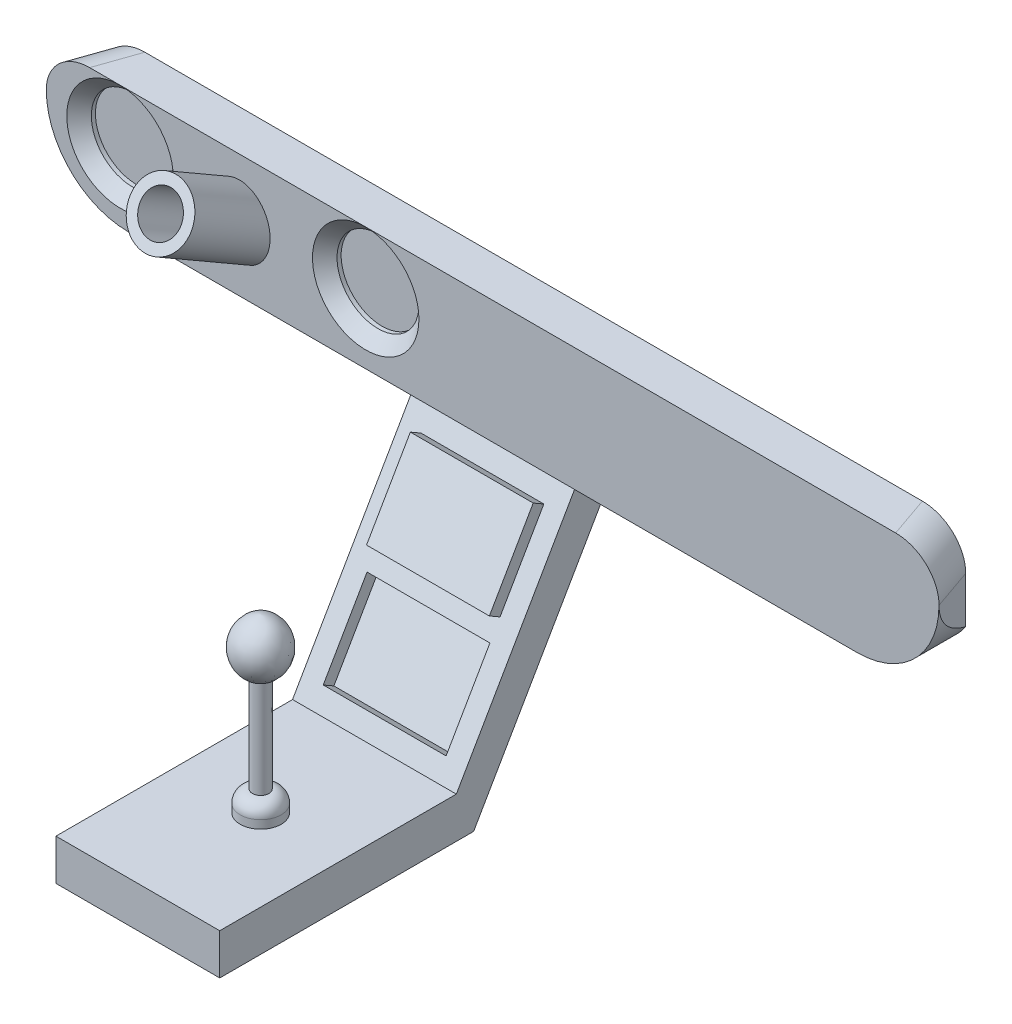
SolidWorks part; units mm, degrees
ref_plane "Ön Düzlem" through (0, 0, 0) normal (0, 0, 1) x (1, 0, 0)
ref_plane "Üst Düzlem" through (0, 0, 0) normal (0, 1, 0) x (1, 0, 0)
ref_plane "Sağ Düzlem" through (0, 0, 0) normal (1, 0, 0) x (0, 0, -1)
sketch "Çizim1" plane through (0, 0, 0) normal (0, 0, 1) x (1, 0, 0)
  line L1 (109, -15) -> (-109, -15)
  line L2 (109, -15) -> (109, 15)
  line L3 (109, 15) -> (-109, 15)
  line L4 (-109, -15) -> (-109, 15)
  line L5 (109, -15) -> (-109, 15) construction
  line L6 (109, 15) -> (-109, -15) construction
  point P0 (0, 0)
  dimension "D1" = 218
  dimension "D2" = 30
extrude "Yükseklik-Ekstrüzyon1" add sketch "Çizim1" along normal mid plane 10
fillet "Radyus1" radius 20 2 edges at (109, -15, 0) (-109, -15, 0)
sketch "Çizim3" plane through (0, 0, 5) normal (0, 0, 1) x (1, 0, 0)
  line L0 (-109, 15) -> (-109, 5) construction
  line L1 (109, 15) -> (-109, 15) construction
  circle A0 centre (-91, 2) radius 10
  circle A1 centre (-31, 2) radius 10
  dimension "D3" = 13
  dimension "D4" = 20
  dimension "D1" = 60
  dimension "D2" = 18
extrude "Kes-Ekstrüzyon1" cut sketch "Çizim3" against normal blind 4
chamfer "Pah1" distance 3 angle 45 2 edges at (-21, 2, 5) (-81, 2, 5)
ref_plane "Düzlem1" through (-61.85, 0, 0) normal (1, 0, 0) x (0, 0, -1)
sketch "Çizim4" plane through (-61.85, 0, 0) normal (1, 0, 0) x (0, 0, -1)
  line L0 (-20.4987, 18.4952) -> (-24.2487, 12)
  line L1 (-20.4987, 18.4952) -> (14.1423, -1.5048)
  line L2 (-24.2487, 12) -> (10.3923, -8)
  line L3 (14.1423, -1.5048) -> (10.3923, -8)
  line L4 (-5, 5) -> (-5, -15) construction
  line L5 (5, -15) -> (-5, -15) construction
  point P0 (0, -2)
  point P3 (0, 0)
  dimension "D1" = 40
  dimension "D2" = 28
  dimension "D3" = 7.5
  dimension "D4" = 120
  dimension "D5" = 13
revolve "Döndür1" add sketch "Çizim4" angle 360 about L2
sketch "Çizim5" plane through (0, 13.5, 23.3827) normal (0, 0.5, 0.866) x (1, 0, 0)
  circle A0 centre (-61.85, -1.7321) radius 5
  point P3 (0, 0)
  dimension "D1" = 10
extrude "Kes-Ekstrüzyon3" cut sketch "Çizim5" against normal through all contours A0
sketch "Çizim7" plane through (0, 0, 0) normal (1, 0, 0) x (0, 0, -1)
  line L0 (5, -15) -> (-5, -15) construction
  line L1 (5, -15) -> (-5, -15)
  line L2 (5, -15) -> (-29.641, -75)
  line L3 (-29.641, -75) -> (-91.641, -75)
  line L4 (-5, 15) -> (5, 15) construction
  line L5 (-5, -15) -> (-33.8675, -65)
  line L6 (-33.8675, -65) -> (-91.641, -65)
  line L7 (-91.641, -65) -> (-91.641, -75)
  dimension "D1" = 90
  dimension "D2" = 120
  dimension "D3" = 62
  dimension "D4" = 10
extrude "Yükseklik-Ekstrüzyon2" add sketch "Çizim7" along normal mid plane 40
sketch "Çizim9" plane through (0, -1.5849, -2.7452) normal (0, 0.5, 0.866) x (1, 0, 0)
  line L0 (20, -15.4904) -> (-20, -15.4904) construction
  line L1 (15, -41.8904) -> (-15, -41.8904)
  line L2 (15, -41.8904) -> (15, -20.4904)
  line L3 (15, -20.4904) -> (-15, -20.4904)
  line L4 (-15, -41.8904) -> (-15, -20.4904)
  line L5 (15, -41.8904) -> (-15, -20.4904) construction
  line L6 (15, -20.4904) -> (-15, -41.8904) construction
  line L7 (15, -68.2254) -> (-15, -68.2254)
  line L8 (15, -68.2254) -> (15, -46.8254)
  line L9 (15, -46.8254) -> (-15, -46.8254)
  line L10 (-15, -68.2254) -> (-15, -46.8254)
  line L11 (15, -68.2254) -> (-15, -46.8254) construction
  line L12 (15, -46.8254) -> (-15, -68.2254) construction
  line L13 (20, -15.4904) -> (20, -73.2254) construction
  line L14 (-20, -15.4904) -> (-20, -73.2254) construction
  line L15 (20, -73.2254) -> (-20, -73.2254) construction
  point P0 (0, -31.1904)
  point P5 (0, -57.5254)
  dimension "D1" = 5
  dimension "D2" = 5
  dimension "D3" = 5
  dimension "D4" = 21.4
  dimension "D5" = 21.4
  dimension "D6" = 5
extrude "Yükseklik-Ekstrüzyon3" add sketch "Çizim9" along normal blind 3 contours L4 L1 L2 L3 region at (0, -28.5966, 12.85)
extrude "Kes-Ekstrüzyon4" cut sketch "Çizim9<3>" against normal blind 3 contours L10 L7 L8 L9 region at (0, -51.4034, 26.0175)
sketch "Çizim9<3>" plane through (0, -1.5849, -2.7452) normal (0, 0.5, 0.866) x (1, 0, 0) same geometry as "Çizim9"
sketch "Çizim11" plane through (0, 0, 0) normal (1, 0, 0) x (0, 0, -1)
  line L0 (-61.641, -23.1477) -> (-61.641, -85)
  line L1 (-61.641, -85) -> (-54.141, -85)
  line L2 (-54.141, -85) -> (-54.141, -75)
  line L3 (-91.641, -75) -> (-29.641, -75) construction
  line L4 (-54.141, -75) -> (-56.641, -75)
  line L5 (-56.641, -75) -> (-56.641, -63)
  line L6 (-59.641, -60) -> (-59.641, -36.2523)
  line L7 (-91.641, -65) -> (-91.641, -75) construction
  line L9 (-33.8675, -65) -> (-91.641, -65) construction
  arc A0 (-56.641, -63) -> (-59.641, -60) centre (-59.641, -63) ccw
  arc A1 (-61.641, -23.1477) -> (-59.641, -36.2523) centre (-62.6068, -30) cw
  dimension "D6" = 3
  dimension "D9" = 6.92
  dimension "D1" = 7.5
  dimension "D2" = 30
  dimension "D3" = 10
  dimension "D4" = 5
  dimension "D5" = 2
  dimension "D7" = 2
  dimension "D8" = 35
revolve "Döndür2" add sketch "Çizim11" angle 360 about L0
sketch "Çizim12" plane through (0, 15, 0) normal (0, 1, 0) x (1, 0, 0)
  line L0 (-109, 5) -> (-109, -5)
  line L1 (-109, -5) -> (-105.52, 5)
  line L2 (109, 5) -> (-109, 5) construction
  line L3 (-105.52, 5) -> (-109, 5)
  dimension "D1" = 3.48
extrude "Kes-Ekstrüzyon5" cut sketch "Çizim12" against normal blind 40
fillet "Radyus2" radius 10 1 edges at (-107.26, 15, 0)
mirror "Aynalama1" about plane through (0, 0, 0) normal (1, 0, 0) of "Radyus2", "Kes-Ekstrüzyon5"
